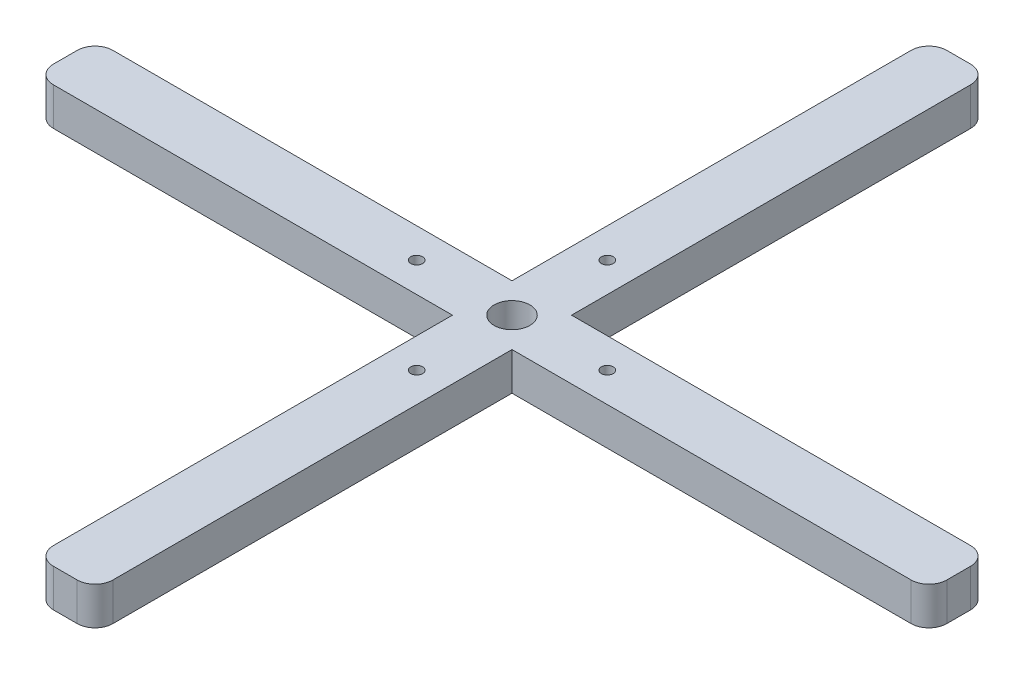
SolidWorks part; units mm, degrees
material "Balsa"
ref_plane "Front Plane" through (0, 0, 0) normal (0, 0, 1) x (1, 0, 0)
ref_plane "Top Plane" through (0, 0, 0) normal (0, 1, 0) x (1, 0, 0)
ref_plane "Right Plane" through (0, 0, 0) normal (1, 0, 0) x (0, 0, -1)
sketch "Sketch1" plane through (0, 0, 0) normal (0, 1, 0) x (1, 0, 0)
  line L0 (80, 80) -> (150, 80)
  line L1 (0, 80) -> (70, 80)
  line L2 (0, 80) -> (0, 70)
  line L3 (0, 70) -> (70, 70)
  line L4 (150, 80) -> (150, 70)
  line L5 (70, 150) -> (80, 150)
  line L6 (70, 150) -> (70, 80)
  line L7 (70, 0) -> (80, 0)
  line L8 (80, 150) -> (80, 80)
  line L9 (70, 70) -> (70, 0)
  line L10 (80, 70) -> (150, 70)
  line L11 (80, 70) -> (80, 0)
  line L12 (0, 70) -> (0, 0) construction
  line L13 (70, 0) -> (0, 0) construction
  dimension "D1" = 10
  dimension "D2" = 150
extrude "main shape" add sketch "Sketch1" along normal blind 6.35
sketch "base X hole location" plane through (0, 6.35, 0) normal (0, 1, 0) x (1, 0, 0)
  line L0 (75, 150) -> (75, 0) construction
  line L1 (59, 91) -> (91, 91) construction
  line L2 (59, 91) -> (59, 59) construction
  line L3 (59, 59) -> (91, 59) construction
  line L4 (91, 91) -> (91, 59) construction
  line L5 (80, 150) -> (70, 150) construction
  line L6 (70, 0) -> (80, 0) construction
  line L7 (0, 75) -> (150, 75) construction
  line L8 (0, 80) -> (0, 70) construction
  line L9 (150, 70) -> (150, 80) construction
  line L10 (59, 91) -> (91, 59) construction
  line L11 (59, 59) -> (91, 91) construction
  point P16 (75, 75)
  point P17 (75, 75)
  point P18 (75, 91)
  point P19 (91, 75)
  point P20 (75, 59)
  point P21 (59, 75)
  dimension "D1" = 32
hole_wizard "base X holes" positions "Sketch4" profile "Sketch3" tap size "#3-48" standard "Ansi Inch"
sketch "Sketch4" plane through (0, 6.35, 0) normal (0, 1, 0) x (-1, 0, 0)
  point P1 (-75, -91)
  point P4 (-59, -75)
  point P7 (-75, -59)
  point P10 (-91, -75)
sketch "Sketch3" plane through (75, 6.35, -91) normal (1, 0, 0) x (0, 0, 1)
  line L0 (0, 0) -> (0, 8.269)
  line L1 (0, 8.269) -> (0.9969, 7.67)
  line L2 (0.9969, 7.67) -> (0.9969, 0)
  line L5 (0.9969, 0) -> (0, 0)
  line L10 (0, 8.269) -> (-0.997, 7.67) construction
  line L11 (0, -6.35) -> (0, 107.95) construction
  dimension "Tap Drill Dia." = 1.9939
  dimension "Tap Drill Depth" = 7.67
  dimension "Drill Angle" = 118
cosmetic thread "Hole Thread1" parameters "D1"=5.03, "D2"=2.5146
cosmetic thread "Hole Thread2" parameters "D1"=5.03, "D2"=2.5146
cosmetic thread "Hole Thread3" parameters "D1"=5.03, "D2"=2.5146
cosmetic thread "Hole Thread4" parameters "D1"=5.03, "D2"=2.5146
ref_axis "Axis1" through (75, 6.35, -75) along (0, 1, 0)
fillet "Fillet1" radius 3 8 edges at (70, 3.175, 0) (80, 3.175, 0) (150, 3.175, -70) (150, 3.175, -80) (80, 3.175, -150) (70, 3.175, -150) (0, 3.175, -80) (0, 3.175, -70)
sketch "Sketch5" plane through (0, 0, 0) normal (0, 1, 0) x (1, 0, 0)
  circle A0 centre (75, 75) radius 3
  dimension "D1" = 6
extrude "cutout for mounting screw" cut sketch "Sketch5" along normal through all
